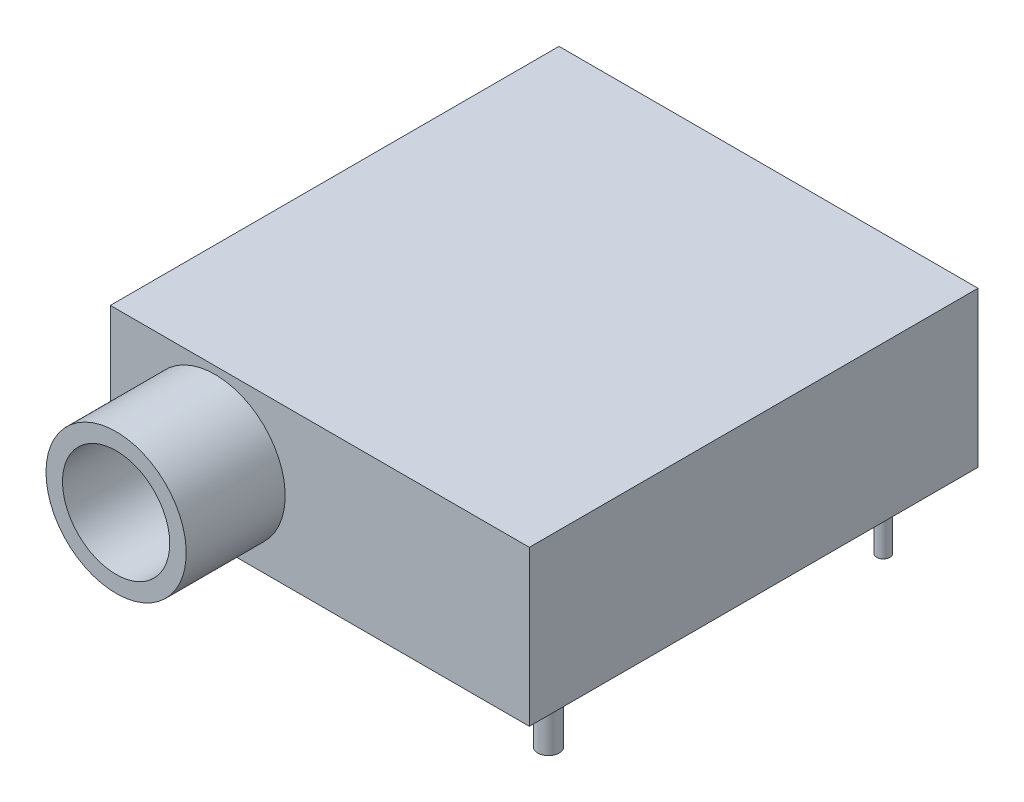
SolidWorks part; units mm, degrees
ref_plane "前视基准面" through (0, 0, 0) normal (0, 0, 1) x (1, 0, 0)
ref_plane "上视基准面" through (0, 0, 0) normal (0, 1, 0) x (1, 0, 0)
ref_plane "右视基准面" through (0, 0, 0) normal (1, 0, 0) x (0, 0, -1)
sketch "草图1" plane through (0, 0, 0) normal (0, 1, 0) x (1, 0, 0)
  line L0 (0, 44.4214) -> (0, -57.1546) construction
  line L1 (-12.7, 13.6) -> (12.7, 13.6)
  line L2 (-12.7, 13.6) -> (-12.7, -13.6)
  line L3 (-12.7, -13.6) -> (12.7, -13.6)
  line L4 (12.7, 13.6) -> (12.7, -13.6)
  line L5 (-47.0259, 0) -> (45.8683, 0) construction
  dimension "D1" = 25.4
  dimension "D2" = 27.2
extrude "凸台-拉伸1" add sketch "草图1" along normal blind 4.7 and the other way blind 4.7
sketch "草图2" plane through (0, 0, 13.6) normal (0, 0, 1) x (1, 0, 0)
  line L0 (3.3126, 0) -> (-16.9837, 0) construction
  line L1 (0, -5.5296) -> (0, 15.0399) construction
  circle A0 centre (-6.35, 0) radius 4.25
  dimension "D2" = 8.5
  dimension "D3" = 6.35
extrude "凸台-拉伸2" add sketch "草图2" along normal offset from surface (6 mm away) 33.2 up to face at (0, 0, -13.6)
sketch "草图3" plane through (0, 0, 19.6) normal (0, 0, 1) x (1, 0, 0)
  arc A3 (-3.1, 0) -> (-3.1, 0) centre (-6.35, 0) ccw
  circle A4 centre (-6.35, 0) radius 3.25
  dimension "D1" = 1
extrude "切除-拉伸1" cut sketch "草图3" against normal blind 5
sketch "草图4" plane through (0, -4.7, 0) normal (0, -1, 0) x (1, 0, 0)
  line L0 (0, -16.9421) -> (0, 22.7553) construction
  line L3 (-3.1, 19.6) -> (-9.6, 19.6) construction
  line L4 (-21.8184, -10.4) -> (16.1038, -10.4) construction
  circle A0 centre (-10.16, 9.9) radius 0.65
  circle A1 centre (10.16, 9.9) radius 0.65
  circle A2 centre (-10.16, -10.4) radius 0.4
  circle A3 centre (-7.62, -10.4) radius 0.4
  circle A4 centre (-5.08, -10.4) radius 0.4
  circle A5 centre (-2.54, -10.4) radius 0.4
  circle A6 centre (0, -10.4) radius 0.4
  circle A7 centre (2.54, -10.4) radius 0.4
  circle A8 centre (5.08, -10.4) radius 0.4
  circle A9 centre (7.62, -10.4) radius 0.4
  circle A10 centre (10.16, -10.4) radius 0.4
  dimension "D3" = 1.3
  dimension "D5" = 0.8
  dimension "D1" = 20.32
  dimension "D2" = 9.7
  dimension "D4" = 20.3
  dimension "D6" = 9
extrude "凸台-拉伸3" add sketch "草图4" along normal blind 4.2
